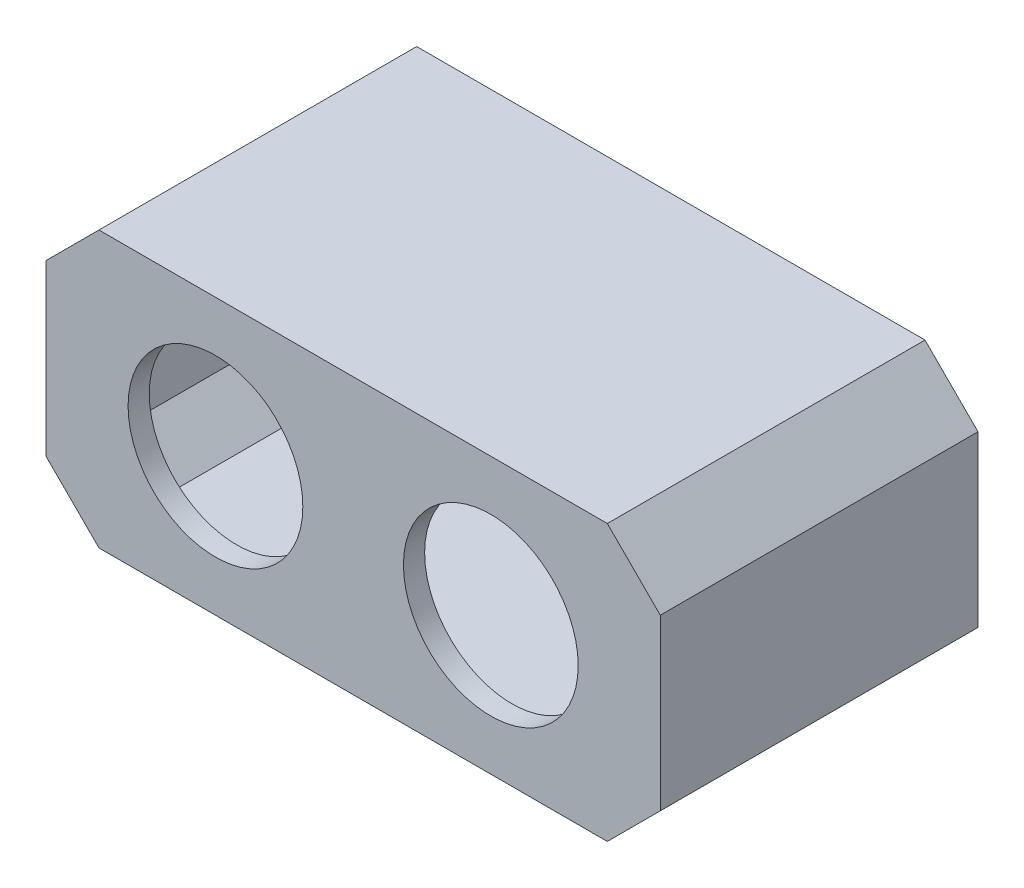
SolidWorks part; units mm, degrees
ref_plane "Front Plane" through (0, 0, 0) normal (0, 0, 1) x (1, 0, 0)
ref_plane "Top Plane" through (0, 0, 0) normal (0, 1, 0) x (1, 0, 0)
ref_plane "Right Plane" through (0, 0, 0) normal (1, 0, 0) x (0, 0, -1)
sketch "Sketch1" plane through (0, 0, 0) normal (0, 0, 1) x (1, 0, 0)
  line L1 (-29, -13) -> (29, -13)
  line L2 (-29, -13) -> (-29, 13)
  line L3 (-29, 13) -> (29, 13)
  line L4 (29, -13) -> (29, 13)
  line L5 (-29, -13) -> (29, 13) construction
  line L6 (-29, 13) -> (29, -13) construction
  point P0 (0, 0)
  dimension "D1" = 58
  dimension "D2" = 26
extrude "skull block" add sketch "Sketch1" against normal blind 30
chamfer "skull chamfer" distance 5 angle 45 4 edges at (29, -13, -15) (-29, -13, -15) (-29, 13, -15) (29, 13, -15)
shell "hollow skull" thickness 2 removed face at (0, 0, -30)
sketch "Sketch2" plane through (0, 0, 0) normal (0, 0, 1) x (1, 0, 0)
  line L0 (0, 0) -> (0, 50000) construction
  line L1 (0, 0) -> (50000, 0) construction
  circle A0 centre (13, 0) radius 8.25
  dimension "D1" = 16.5
  dimension "D2" = 13
extrude "eye hole" cut sketch "Sketch2" against normal up to next
mirror "mirror eye hole" about plane through (0, 0, 0) normal (1, 0, 0) of "eye hole"
sketch "Sketch3" plane through (0, -13, 0) normal (0, -1, 0) x (1, 0, 0)
  line L0 (0, 0) -> (0, -30) construction
  line L1 (-24, -30) -> (24, -30) construction
  circle A0 centre (0, -15) radius 12
  dimension "D1" = 24
extrude "neck mount" cut sketch "Sketch3" against normal blind 1
